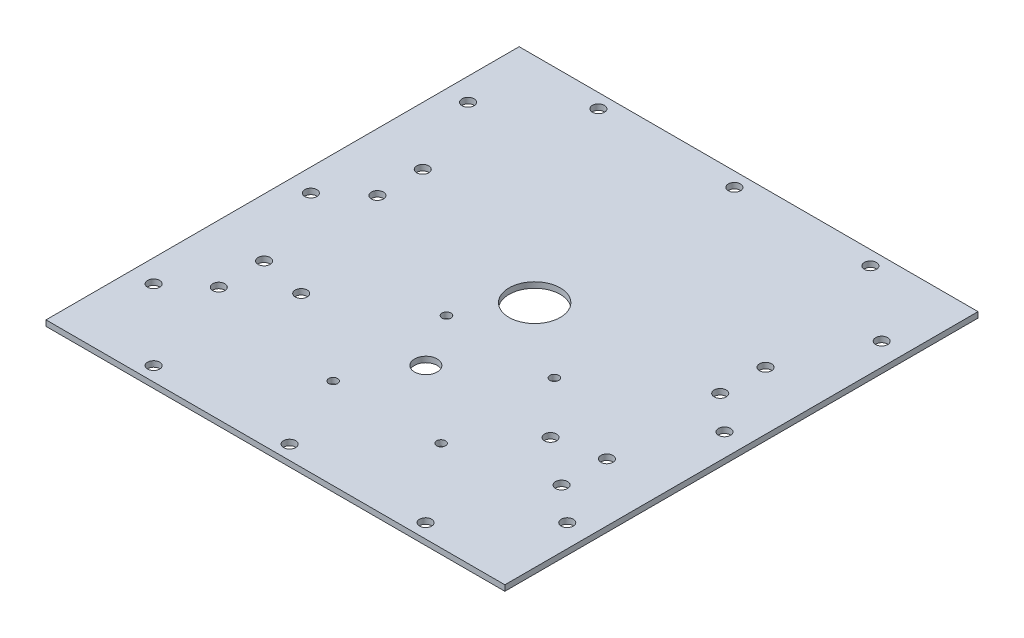
SolidWorks part; units mm, degrees
material "5052-H32"
ref_plane "Front Plane" through (0, 0, 0) normal (0, 0, 1) x (1, 0, 0)
ref_plane "Top Plane" through (0, 0, 0) normal (0, 1, 0) x (1, 0, 0)
ref_plane "Right Plane" through (0, 0, 0) normal (1, 0, 0) x (0, 0, -1)
sketch "Sketch1" plane through (0, 0, 0) normal (0, 1, 0) x (1, 0, 0)
  line L0 (-254, 178.5938) -> (-254, 64.2938) construction
  line L1 (-315.9125, 0) -> (0, 0)
  line L2 (-315.9125, 0) -> (-315.9125, 265.1125)
  line L3 (-315.9125, 265.1125) -> (0, 265.1125)
  line L4 (0, 0) -> (0, 265.1125)
  line L5 (-157.9562, -734.8875) -> (-157.9563, 49265.1125) construction
  line L6 (-234.1562, 7.9375) -> (-81.7562, 7.9375) construction
  line L7 (-181.0702, 44.4182) -> (-111.2202, 44.4182) construction
  line L8 (-181.0702, 44.4182) -> (-181.0702, 120.6182) construction
  line L9 (-181.0702, 120.6182) -> (-111.2202, 120.6182) construction
  line L10 (-111.2202, 44.4182) -> (-111.2202, 120.6182) construction
  line L11 (-176.3712, 114.2682) -> (-115.9192, 114.2682) construction
  line L12 (-176.3712, 114.2682) -> (-176.3712, 50.7682) construction
  line L13 (-176.3712, 50.7682) -> (-115.9192, 50.7682) construction
  line L14 (-115.9192, 114.2682) -> (-115.9192, 50.7682) construction
  line L15 (-234.1562, 257.175) -> (-81.7562, 257.175) construction
  line L16 (-227.8062, 84.2962) -> (-88.1063, 84.2963) construction
  line L17 (-273.8438, 223.8375) -> (-273.8438, 47.625) construction
  circle A0 centre (-254, 64.2938) radius 3.3782
  circle A1 centre (-254, 89.6937) radius 3.3782
  circle A2 centre (-254, 153.1937) radius 3.3782
  circle A3 centre (-254, 178.5938) radius 3.3782
  circle A4 centre (-61.9125, 64.2938) radius 3.3782
  circle A5 centre (-61.9125, 89.6937) radius 3.3782
  circle A6 centre (-61.9125, 153.1937) radius 3.3782
  circle A7 centre (-61.9125, 178.5938) radius 3.3782
  circle A8 centre (-157.9562, 145.2562) radius 14.351
  circle A9 centre (-157.9562, 84.2962) radius 6.35
  circle A10 centre (-176.3712, 114.2682) radius 2.4892
  circle A11 centre (-115.9192, 114.2682) radius 2.4892
  circle A12 centre (-115.9192, 50.7682) radius 2.4892
  circle A13 centre (-176.3712, 50.7682) radius 2.4892
  circle A14 centre (-234.1562, 7.9375) radius 3.3782
  circle A15 centre (-157.9562, 7.9375) radius 3.3782
  circle A16 centre (-81.7562, 7.9375) radius 3.3782
  circle A17 centre (-157.9562, 257.175) radius 3.3782
  circle A18 centre (-81.7562, 257.175) radius 3.3782
  circle A19 centre (-234.1562, 257.175) radius 3.3782
  circle A20 centre (-227.8062, 84.2962) radius 3.3782
  circle A21 centre (-88.1063, 84.2963) radius 3.3782
  circle A22 centre (-273.8438, 223.8375) radius 3.3782
  circle A23 centre (-273.8438, 135.7312) radius 3.3782
  circle A24 centre (-273.8438, 47.625) radius 3.3782
  circle A25 centre (-42.0687, 223.8375) radius 3.3782
  circle A26 centre (-42.0687, 135.7312) radius 3.3782
  circle A27 centre (-42.0687, 47.625) radius 3.3782
  point P4 (-157.9562, 265.1125)
  point P48 (-157.9562, 84.2962)
  point P55 (-157.9562, 84.2962)
  point P60 (-273.8438, 135.7312)
  dimension "D3" = 6.7564
  dimension "D4" = 6.7564
  dimension "D5" = 6.7564
  dimension "D6" = 6.7564
  dimension "D12" = 28.702
  dimension "D23" = 12.7
  dimension "D24" = 4.9784
  dimension "D25" = 4.9784
  dimension "D26" = 4.9784
  dimension "D27" = 4.9784
  dimension "D29" = 6.7564
  dimension "D30" = 6.7564
  dimension "D31" = 6.7564
  dimension "D34" = 6.7564
  dimension "D35" = 6.7564
  dimension "D36" = 6.7564
  dimension "D39" = 6.7564
  dimension "D40" = 6.7564
  dimension "D41" = 6.7564
  dimension "D42" = 6.7564
  dimension "D43" = 6.7564
  dimension "D1" = 315.9125
  dimension "D2" = 265.1125
  dimension "D7" = 25.4
  dimension "D8" = 25.4
  dimension "D9" = 64.2938
  dimension "D10" = 86.5187
  dimension "D11" = 61.9125
  dimension "D13" = 119.8563
  dimension "D14" = 76.2
  dimension "D15" = 69.85
  dimension "D16" = 23.114
  dimension "D17" = 60.452
  dimension "D18" = 60.96
  dimension "D19" = 36.322
  dimension "D20" = 4.699
  dimension "D21" = 6.35
  dimension "D22" = 6.35
  dimension "D28" = 7.9375
  dimension "D32" = 152.4
  dimension "D33" = 152.4
  dimension "D37" = 7.9375
  dimension "D38" = 139.7
  dimension "D44" = 42.0688
  dimension "D45" = 176.2125
  dimension "D46" = 41.275
base flange "Base-Flange1" sketch "Sketch1" thickness 3.175 reverse thickness direction no parameters "D1"=0.7366
sketch "Sketch2" plane through (0, 0, 0) normal (0, 1, 0) x (1, 0, 0)
  line L0 (-315.9125, 0) -> (0, 0) construction
  line L1 (-315.9125, 265.1125) -> (-286.5125, 265.1125)
  line L2 (-315.9125, 265.1125) -> (-315.9125, 0)
  line L3 (-315.9125, 0) -> (-286.5125, 0)
  line L4 (-286.5125, 265.1125) -> (-286.5125, 0)
  line L5 (-157.9562, 145.2562) -> (-157.9562, 0) construction
  line L6 (0, 0) -> (-29.4, 0)
  line L7 (0, 265.1125) -> (0, 0)
  line L8 (-29.4, 265.1125) -> (-29.4, 0)
  line L9 (0, 265.1125) -> (-29.4, 265.1125)
  dimension "D1" = 29.4
extrude "Cut-Extrude1" cut sketch "Sketch2" against normal through all normal cut yes
sketch "Bend-Lines1" [suppressed] plane through (0, 0, 0) normal (0, 1, 0) x (1, 0, 0)
sketch "Bounding-Box1" [suppressed] plane through (0, 0, 0) normal (0, 1, 0) x (1, 0, 0)
sheet metal parameters "Sheet-Metal1" thickness 3.175 parameters "D1"=0.7366
flat pattern "Flat-Pattern1" [suppressed]
sketch "Bend-Lines2" plane through (0, 0, 0) normal (0, 1, 0) x (1, 0, 0)
sketch3d "Bounding-Box2" [suppressed]
  line L0 (0, 265.1125, 0) -> (-315.9125, 265.1125, 0) construction
  line L1 (0, 0, 0) -> (-315.9125, 0, 0) construction
  line L2 (0, 265.1125, 0) -> (0, 0, 0) construction
  line L3 (-315.9125, 265.1125, 0) -> (-315.9125, 0, 0) construction
sheet metal parameters "Sheet-Metal3" thickness 3.175 parameters "D1"=0.7366
flat pattern "Flat-Pattern1"
sketch "Bend-Lines2" plane through (0, 0, 0) normal (0, 1, 0) x (1, 0, 0)
sketch3d "Bounding-Box2" [suppressed]
  line L0 (-286.5125, 0, 0) -> (-286.5125, 265.1125, 0) construction
  line L1 (-29.4, 0, 0) -> (-29.4, 265.1125, 0) construction
  line L2 (-286.5125, 0, 0) -> (-29.4, 0, 0) construction
  line L3 (-286.5125, 265.1125, 0) -> (-29.4, 265.1125, 0) construction
